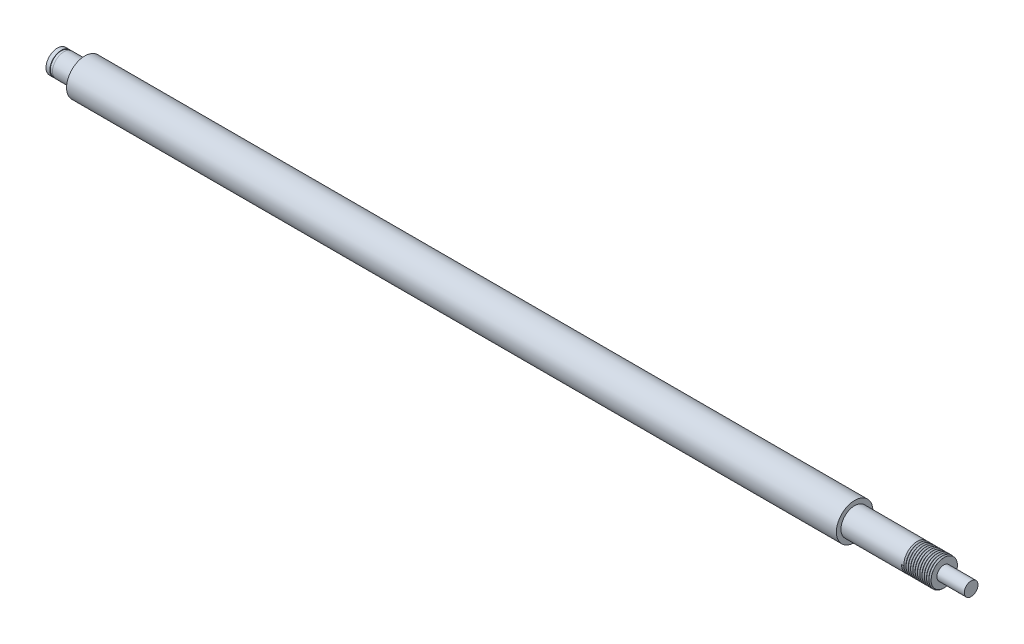
SolidWorks part; units mm, degrees
material "Хромистая нержавеющая сталь"
ref_plane "Спереди" through (0, 0, 0) normal (0, 0, 1) x (1, 0, 0)
ref_plane "Сверху" through (0, 0, 0) normal (0, 1, 0) x (1, 0, 0)
ref_plane "Справа" through (0, 0, 0) normal (1, 0, 0) x (0, 0, -1)
sketch "Эскиз1" plane through (0, 0, 0) normal (0, 0, 1) x (1, 0, 0)
  line L0 (-313.0019, 5.9419) -> (-313.0019, 10.9419)
  line L1 (-313.0019, 10.9419) -> (-311.3019, 10.9419)
  line L2 (-311.3019, 10.9419) -> (-311.3019, 10.7419)
  line L3 (-311.3019, 10.7419) -> (-310.1519, 10.7419)
  line L4 (-310.1519, 10.7419) -> (-310.1519, 10.9419)
  line L5 (-310.1519, 10.9419) -> (-301.0019, 10.9419)
  line L6 (-301.0019, 10.9419) -> (-301.0019, 13.9419)
  line L7 (-301.0019, 13.9419) -> (35.9981, 13.9419)
  line L8 (35.9981, 13.9419) -> (35.9981, 11.9419)
  line L9 (35.9981, 11.9419) -> (74.9981, 11.9419)
  line L10 (74.9981, 11.9419) -> (74.9981, 8.9419)
  line L11 (74.9981, 8.9419) -> (86.9981, 8.9419)
  line L12 (86.9981, 8.9419) -> (86.9981, 5.9419)
  line L13 (86.9981, 5.9419) -> (-313.0019, 5.9419)
  line L14 (62.9981, 14.6846) -> (62.9981, -1.3142) construction
  dimension "D1" = 1.15
  dimension "D2" = 9.15
  dimension "D3" = 12
  dimension "D4" = 39
  dimension "D5" = 51
  dimension "D6" = 12
  dimension "D7" = 3
  dimension "D8" = 3
  dimension "D9" = 2
  dimension "D10" = 5
  dimension "D11" = 4.8
  dimension "D12" = 5
  dimension "D13" = 400
revolve "Повернуть1" add sketch "Эскиз1" angle 360 about L13
ref_plane "Плоскость1" through (45.9981, 0, 0) normal (1, 0, 0) x (0, 0, -1)
sketch "Эскиз2" plane through (45.9981, 0, 0) normal (1, 0, 0) x (0, 0, -1)
  circle A0 centre (0, 5.9419) radius 8 construction
  circle A1 centre (0, 5.9419) radius 8
curve "Спираль1" pitch 5 height 290 turns 58
sketch "Эскиз3" plane through (0, 0, 0) normal (0, 0, 1) x (1, 0, 0)
  line L0 (-207.8405, -2.5666) -> (-201.4949, -2.5666) construction
  line L1 (-210.2778, -2.0666) -> (-203.5838, -2.0666) construction
  line L2 (-207.8405, -4.8575) -> (-207.8405, -1.8666) construction
  line L3 (-205.3405, -4.8575) -> (-205.3405, -0.2923) construction
  line L4 (-205.3405, -1.8666) -> (-205.4905, -2.0666)
  line L5 (-205.4905, -2.0666) -> (-205.4905, -2.5666)
  line L6 (-205.4905, -2.5666) -> (-205.1905, -2.5666)
  line L7 (-205.1905, -2.5666) -> (-205.1905, -2.0666)
  line L8 (-205.1905, -2.0666) -> (-205.3405, -1.8666)
  circle A0 centre (-207.8405, -2.5666) radius 1.5875
  point P7 (-207.7498, -2.0666)
  dimension "D1" = 3.175
  dimension "D2" = 0.5
  dimension "D3" = 2.5
  dimension "D4" = 0.2
  dimension "D5" = 0.3
ref_plane "Плоскость2" through (84.9981, 0, 0) normal (1, 0, 0) x (0, 0, -1)
sketch "Эскиз4" plane through (84.9981, 0, 0) normal (1, 0, 0) x (0, 0, -1)
  circle A0 centre (0, 5.9419) radius 6 construction
  circle A1 centre (0, 5.9419) radius 6
curve "Спираль2" pitch 1 height 22 radius 6 centre (84.9981, 5.9419, 0) axis (-1, 0, 0) start towards (0, 0, 1)
sketch "Эскиз5" plane through (0, 0, 0) normal (0, 0, 1) x (1, 0, 0)
  line L0 (76.2561, 0.4419) -> (75.7561, -0.0581)
  line L1 (35.9981, -0.0581) -> (74.9981, -0.0581) construction
  line L2 (75.7561, -0.0581) -> (75.7561, -1.0581)
  line L3 (75.7561, -1.0581) -> (76.7561, -1.0581)
  line L4 (76.7561, -1.0581) -> (76.7561, -0.0581)
  line L5 (76.7561, -0.0581) -> (76.2561, 0.4419)
  line L6 (76.2561, 0.4419) -> (76.2561, -0.2584) construction
  line L7 (75.7561, -0.0581) -> (76.7561, -0.0581) construction
  dimension "D1" = 0.5
  dimension "D2" = 1
  dimension "D3" = 1
sweep "Вырез-По траектории7" cut profiles "Эскиз5" path "Спираль2" align with end faces yes
